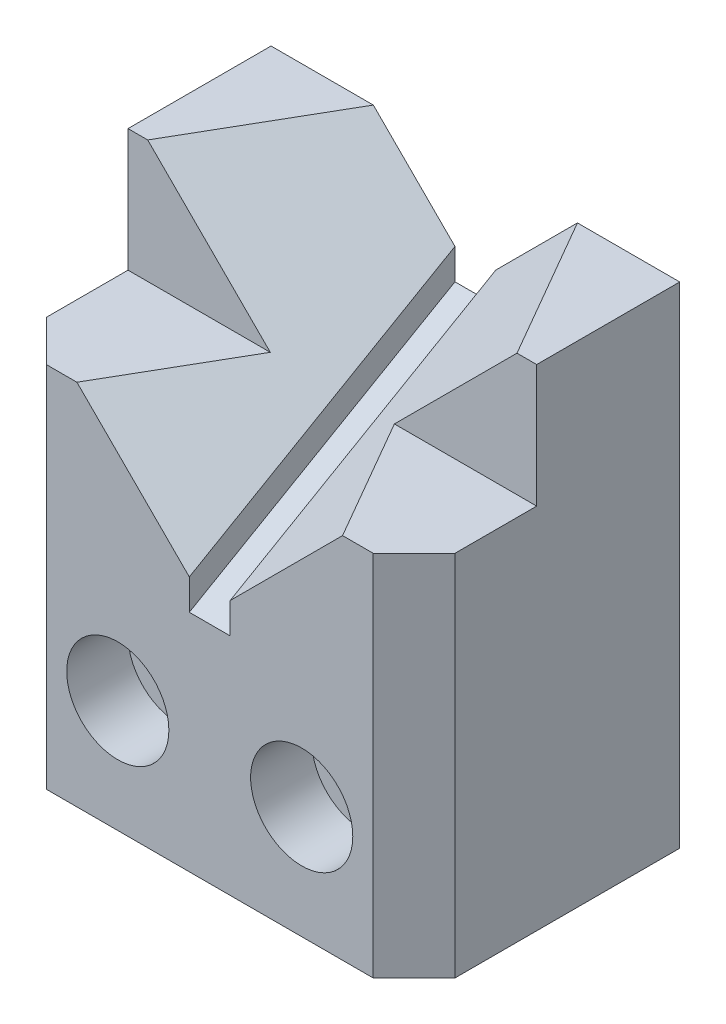
SolidWorks part; units mm, degrees
ref_plane "Front Plane" through (0, 0, 0) normal (0, 0, 1) x (1, 0, 0)
ref_plane "Top Plane" through (0, 0, 0) normal (0, 1, 0) x (1, 0, 0)
ref_plane "Right Plane" through (0, 0, 0) normal (1, 0, 0) x (0, 0, -1)
sketch "Sketch1" plane through (0, 0, 0) normal (1, 0, 0) x (0, 0, -1)
  line L0 (20.6375, 76.2) -> (20.6375, 0)
  line L1 (-20.6375, 0) -> (20.6375, 0)
  line L2 (-20.6375, 0) -> (-20.6375, 57.15)
  line L3 (-20.6375, 57.15) -> (-1.5875, 57.15)
  line L5 (20.6375, 76.2) -> (-1.5875, 76.2)
  line L6 (-1.5875, 76.2) -> (-1.5875, 57.15)
  point P4 (0, 0)
  dimension "D1" = 41.275
  dimension "D2" = 57.15
  dimension "D3" = 76.2
  dimension "D4" = 22.225
extrude "Boss-Extrude1" add sketch "Sketch1" along normal mid plane 63.5
sketch "Sketch2" plane through (0, 0, 20.6375) normal (0, 0, 1) x (1, 0, 0)
  line L0 (0, 0) -> (0, 17.4625) construction
  line L1 (-14.2875, 17.4625) -> (14.2875, 17.4625) construction
  line L2 (31.75, 0) -> (-31.75, 0) construction
  circle A0 centre (14.2875, 17.4625) radius 4.7625
  circle A1 centre (14.2875, 17.4625) radius 7.9375
  circle A2 centre (-14.2875, 17.4625) radius 7.9375
  circle A3 centre (-14.2875, 17.4625) radius 4.7625
  dimension "D3" = 9.525
  dimension "D4" = 15.875
  dimension "D1" = 17.4625
  dimension "D2" = 14.2875
extrude "Cut-Extrude1" cut sketch "Sketch2" against normal blind 9.525 contours A3 | A0 | A1 A0 | A2 A3 region at (14.2875, 17.4625, 20.6375) region at (6.5745, 17.4625, 20.6375) region at (-22.0005, 17.4625, 20.6375) region at (-14.2875, 17.4625, 20.6375)
extrude "Cut-Extrude2" cut sketch "Sketch2<4>" against normal through all contours A3 | A0 region at (14.2875, 17.4625, 20.6375) region at (-14.2875, 17.4625, 20.6375)
sketch "Sketch2<4>" plane through (0, 0, 20.6375) normal (0, 0, 1) x (1, 0, 0) same geometry as "Sketch2"
sketch "Sketch3" plane through (0, 0, 20.6375) normal (0, 0, 1) x (1, 0, 0)
  line L0 (-39.6875, 76.2) -> (-3.175, 39.6875)
  line L1 (31.75, 76.2) -> (-31.75, 76.2) construction
  line L2 (-3.175, 39.6875) -> (-3.175, 34.925)
  line L3 (-3.175, 34.925) -> (3.175, 34.925)
  line L4 (0, 0) -> (0, 76.2) construction
  line L6 (31.75, 57.15) -> (-31.75, 57.15) construction
  line L7 (3.175, 39.6875) -> (3.175, 34.925)
  line L8 (39.6875, 76.2) -> (3.175, 39.6875)
  line L9 (-39.6875, 76.2) -> (39.6875, 76.2)
  point P14 (0, 34.925)
  dimension "D1" = 90
  dimension "D2" = 22.225
  dimension "D3" = 4.7625
  dimension "D4" = 3.175
sketch "Sketch4" plane through (0, 0, 0) normal (1, 0, 0) x (0, 0, -1)
  line L0 (-20.6375, 34.925) -> (20.6375, 58.7551)
  line L1 (20.6375, 0) -> (20.6375, 76.2) construction
  dimension "D1" = 60
extrude "Cut-Extrude3" cut sketch "Sketch3" along direction (0, 0.5, -0.866) on the side against the normal through all contours L0 L2 L3 L7 L8 L9
chamfer "Chamfer1" distance 6.35 angle 45 2 edges at (-31.75, 28.575, 20.6375) (31.75, 28.575, 20.6375)
